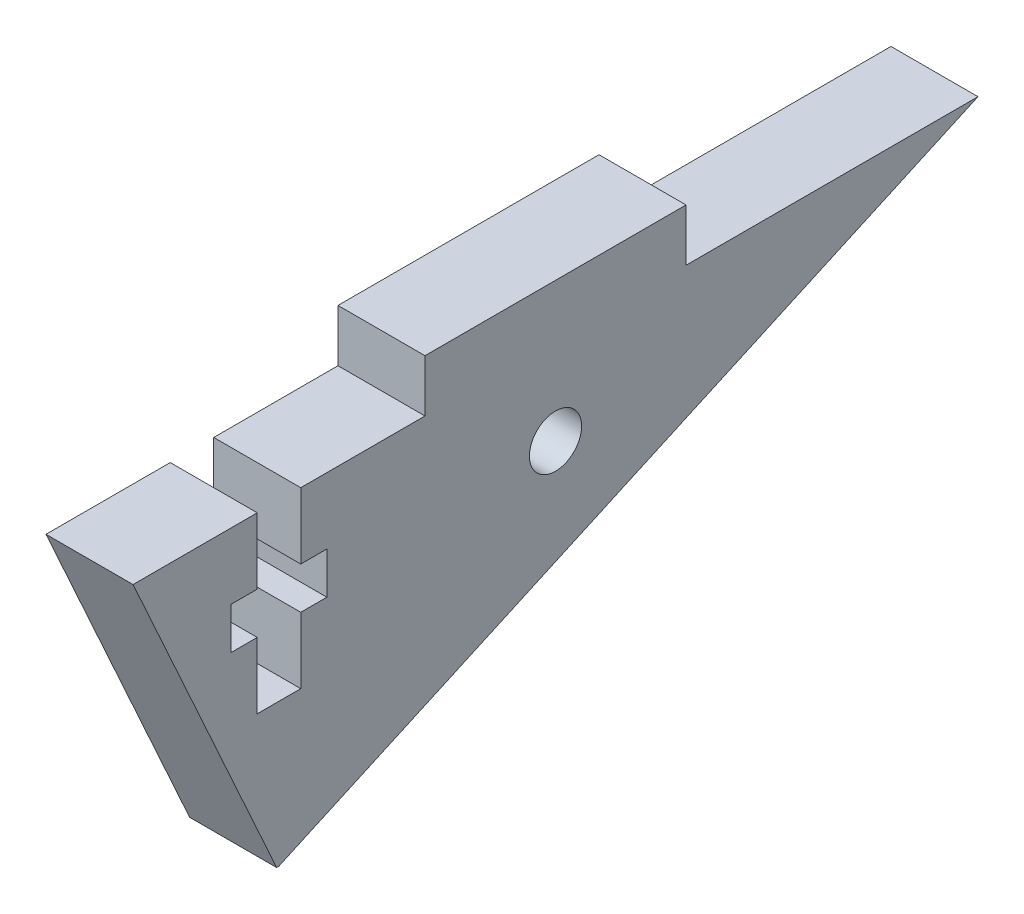
SolidWorks part; units mm, degrees
material "PMMA"
ref_plane "Front Plane" through (0, 0, 0) normal (0, 0, 1) x (1, 0, 0)
ref_plane "Top Plane" through (0, 0, 0) normal (0, 1, 0) x (1, 0, 0)
ref_plane "Right Plane" through (0, 0, 0) normal (1, 0, 0) x (0, 0, -1)
sketch "Schizzo1" plane through (0, 0, 0) normal (1, 0, 0) x (0, 0, -1)
  line L0 (-24.275, -9.105) -> (24.275, 9.105) construction
  line L1 (-24.275, 9.105) -> (24.275, 9.105)
  line L2 (-24.275, 9.105) -> (-24.275, -9.105)
  line L3 (-24.275, -9.105) -> (24.275, -9.105)
  line L4 (24.275, 9.105) -> (24.275, -9.105)
  point P4 (0, 0)
  dimension "D1" = 18.21
  dimension "D2" = 48.55
extrude "Estrusione-Estrusione1" add sketch "Schizzo1" along normal blind 5
sketch "Schizzo3" plane through (0, 0, 0) normal (1, 0, 0) x (0, 0, -1)
  line L1 (24.275, 9.105) -> (-24.275, 9.105) construction
  line L3 (0, 9.105) -> (0, -9.105) construction
  line L4 (-24.275, -9.105) -> (24.275, -9.105) construction
  circle A1 centre (0, 4.105) radius 1.5
  dimension "D5" = 5
sketch "Schizzo2" plane through (0, 0, 0) normal (1, 0, 0) x (0, 0, -1)
  line L0 (24.275, 9.105) -> (-15.906, -9.105)
  line L1 (-24.275, -9.105) -> (24.275, -9.105) construction
  line L2 (-15.906, -9.105) -> (24.275, -9.105)
  line L3 (24.275, -9.105) -> (24.275, 9.105)
  line L4 (-24.275, 9.105) -> (-24.275, -9.105)
  line L5 (-24.275, -9.105) -> (-16.0193, -9.1116)
  line L6 (-16.0193, -9.1116) -> (-24.275, 9.105)
  line L7 (24.275, 9.105) -> (-24.275, 9.105) construction
  dimension "D1" = 24.38
  dimension "D2" = 65.62
  dimension "D3" = 20
extrude "Taglio-Estrusione1" cut sketch "Schizzo2" along direction (1, 0, 0) on the side of the normal through all
extrude "Taglio-Estrusione2" cut sketch "Schizzo3" along direction (1, 0, 0) on the side of the normal through all
sketch "Schizzo4" plane through (0, 9.105, 0) normal (0, 1, 0) x (1, 0, 0)
  line L1 (5, 24.275) -> (5, -24.275) construction
  line L2 (0, 24.275) -> (0, -24.275) construction
  line L4 (5, 24.275) -> (0, 24.275) construction
  line L6 (5, 0) -> (0, 0) construction
  line L7 (0, 7.5) -> (5, 7.5)
  line L8 (0, 7.5) -> (0, -7.5)
  line L9 (0, -7.5) -> (5, -7.5)
  line L10 (5, 7.5) -> (5, -7.5)
  point P16 (5, 0)
  dimension "D2" = 16.775
  dimension "D3" = 15
extrude "Estrusione-Estrusione2" add sketch "Schizzo4" along normal blind 3
sketch "Schizzo6" plane through (0, 0, 0) normal (1, 0, 0) x (0, 0, -1)
  line L0 (-15.8875, -0.895) -> (-15.8875, 9.105) construction
  line L1 (-17.1375, -0.895) -> (-17.1375, 2.905)
  line L2 (-17.1375, 2.905) -> (-18.6375, 2.905)
  line L3 (-18.6375, 2.905) -> (-18.6375, 5.305)
  line L4 (-18.6375, 5.305) -> (-17.1375, 5.305)
  line L5 (-17.1375, 5.305) -> (-17.1375, 9.105)
  line L6 (-17.1375, 9.105) -> (-14.6375, 9.105)
  line L7 (-14.6375, 9.105) -> (-14.6375, 5.305)
  line L8 (-14.6375, 5.305) -> (-13.1375, 5.305)
  line L9 (-13.1375, 5.305) -> (-13.1375, 2.905)
  line L10 (-13.1375, 2.905) -> (-14.6375, 2.905)
  line L11 (-14.6375, 2.905) -> (-14.6375, -0.895)
  line L12 (-14.6375, -0.895) -> (-17.1375, -0.895)
  line L15 (-7.5, 9.105) -> (-24.275, 9.105) construction
  line L16 (-15.8875, 9.105) -> (-15.8875, -9.105) construction
  line L17 (-16.0222, -9.105) -> (-15.906, -9.105) construction
  point P14 (-15.8875, -0.895)
  dimension "D1" = 2.4
  dimension "D2" = 10
  dimension "D3" = 90
  dimension "D4" = 90
  dimension "D5" = 2.5
  dimension "D6" = 5.5
extrude "Taglio-Estrusione3" cut sketch "Schizzo6" along normal through all
equation "\"Thickness5\"= 5"
equation "\"D1@Estrusione-Estrusione1\"=\"Thickness5\""
equation "\"D1@Estrusione-Estrusione2\"=\"Thickness3\""
equation "\"Thickness3\"= 3"
